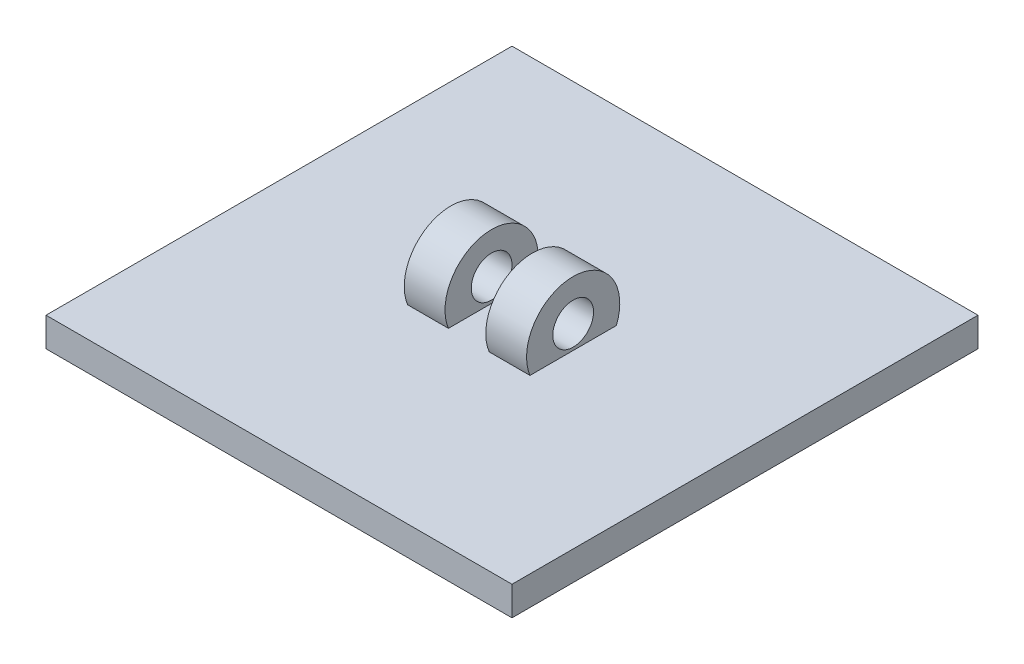
SolidWorks part; units mm, degrees
ref_plane "Front Plane" through (0, 0, 0) normal (0, 0, 1) x (1, 0, 0)
ref_plane "Top Plane" through (0, 0, 0) normal (0, 1, 0) x (1, 0, 0)
ref_plane "Right Plane" through (0, 0, 0) normal (1, 0, 0) x (0, 0, -1)
sketch "Sketch2" plane through (0, 0, 0) normal (0, 1, 0) x (1, 0, 0)
  line L1 (-40, -40) -> (40, -40)
  line L2 (-40, -40) -> (-40, 40)
  line L3 (-40, 40) -> (40, 40)
  line L4 (40, -40) -> (40, 40)
  line L5 (-40, -40) -> (40, 40) construction
  line L6 (-40, 40) -> (40, -40) construction
  point P0 (0, 0)
  dimension "D1" = 80
  dimension "D2" = 80
extrude "Boss-Extrude1" add sketch "Sketch2" along normal blind 5
sketch "Sketch3" plane through (0, 0, 0) normal (1, 0, 0) x (0, 0, -1)
  line L0 (-40, 0) -> (40, 0) construction
  line L1 (0, 0) -> (0.4848, 0)
  circle A0 centre (0, 8) radius 8
  point P2 (0, 7.9622)
  point P6 (0, 0)
  point P9 (0, 0)
  dimension "D1" = 16
  dimension "D2" = 8
extrude "Boss-Extrude2" add sketch "Sketch3" along normal mid plane 21 contours A0 region at (0, 8, 0)
sketch "Sketch4" plane through (0, 0, 0) normal (1, 0, 0) x (0, 0, -1)
  line L0 (-7.4162, 5) -> (7.4162, 5)
  circle A1 centre (0, 8) radius 8
  arc A2 (7.4162, 5) -> (-7.4162, 5) centre (0, 8) ccw construction
extrude "Cut-Extrude3" cut sketch "Sketch4" against normal mid plane 7 contours L0 A1 region at (0, 9.8451, 0)
sketch "Sketch8" plane through (10.5, 0, 0) normal (1, 0, 0) x (0, 0, -1)
  line L1 (7.4162, 5) -> (-7.4162, 5) construction
  circle A0 centre (0, 9) radius 3.5
  point P2 (0, 0)
  point P4 (0, 0)
  point P5 (0, 0)
  dimension "D1" = 7
  dimension "D2" = 4
extrude "Cut-Extrude5" cut sketch "Sketch8" against normal through all
equation "\"D2@Sketch3\"=\"D1@Sketch3\"/2"
